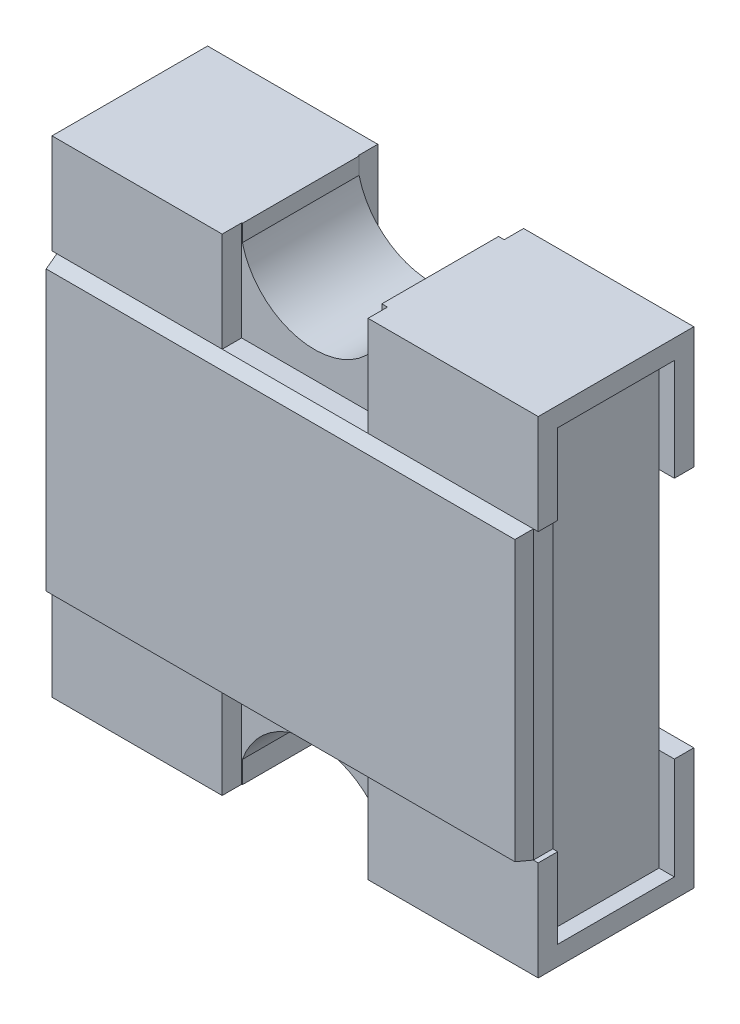
SolidWorks part; units mm, degrees
ref_plane "Спереди" through (0, 0, 0) normal (0, 0, 1) x (1, 0, 0)
ref_plane "Сверху" through (0, 0, 0) normal (0, 1, 0) x (1, 0, 0)
ref_plane "Справа" through (0, 0, 0) normal (1, 0, 0) x (0, 0, -1)
sketch "Эскиз1" plane through (0, 0, 0) normal (0, 0, 1) x (1, 0, 0)
  line L0 (-0.1484, 0.5) -> (-0.1484, 0.4655)
  line L1 (0.1384, 0.5) -> (0.1384, 0.4372)
  line L2 (0, 0) -> (0.4684, 0) construction
  line L3 (0.1384, -0.5) -> (0.1384, -0.4321)
  line L4 (0.4684, 0.5) -> (0.4684, -0.5)
  line L5 (-0.1484, -0.5) -> (-0.1484, -0.4549)
  line L6 (-0.4784, 0.5) -> (-0.4784, -0.5)
  line L9 (0.1384, 0.5) -> (0.4684, 0.5)
  line L11 (0.1384, -0.5) -> (0.4684, -0.5)
  line L13 (-0.1484, 0.5) -> (-0.4784, 0.5)
  line L15 (-0.1484, -0.5) -> (-0.4784, -0.5)
  arc A0 (-0.1484, 0.4655) -> (0.1384, 0.4372) centre (0, 0.5022) ccw
  arc A1 (-0.1484, -0.4549) -> (0.1384, -0.4321) centre (0, -0.5067) cw
  point P7 (-0.0124, -0.35)
  point P9 (-0.015, 0.35)
  point P16 (-0.4784, 0)
  point P17 (0.4684, 0)
  dimension "D1" = 0.33
  dimension "D2" = 0.33
  dimension "D3" = 1
  dimension "D4" = 0.15
  dimension "D5" = 0.15
extrude "Вытянуть1" add sketch "Эскиз1" along normal blind 0.24 from offset 0.04
sketch "Эскиз2" plane through (0, 0, 0) normal (0, 0, 1) x (1, 0, 0)
  line L1 (-0.49, 0.295) -> (0.49, 0.295)
  line L2 (-0.49, 0.295) -> (-0.49, -0.295)
  line L3 (-0.49, -0.295) -> (0.49, -0.295)
  line L4 (0.49, 0.295) -> (0.49, -0.295)
extrude "Бобышка-Вытянуть1" add sketch "Эскиз2" along normal blind 0.03 draft 15 and the other way blind 0.04 from offset 0.32
sketch "Эскиз3" plane through (0, 0, 0) normal (1, 0, 0) x (0, 0, -1)
  line L0 (-0.32, 0.295) -> (-0.28, 0.295)
  line L1 (-0.32, 0.5) -> (0, 0.5)
  line L2 (-0.32, 0.5) -> (-0.32, 0.295)
  line L4 (0, 0.5) -> (0, 0.25)
  line L5 (-0.28, 0.295) -> (-0.28, 0.46)
  line L6 (-0.28, 0.46) -> (-0.04, 0.46)
  line L7 (-0.04, 0.46) -> (-0.04, 0.25)
  line L9 (-0.04, 0.25) -> (0, 0.25)
  line L10 (0, 0) -> (-0.5306, 0) construction
  line L11 (-0.04, -0.25) -> (0, -0.25)
  line L12 (-0.04, -0.46) -> (-0.04, -0.25)
  line L13 (-0.28, -0.46) -> (-0.04, -0.46)
  line L14 (-0.28, -0.295) -> (-0.28, -0.46)
  line L15 (0, -0.5) -> (0, -0.25)
  line L16 (-0.32, -0.5) -> (-0.32, -0.295)
  line L17 (-0.32, -0.5) -> (0, -0.5)
  line L18 (-0.32, -0.295) -> (-0.28, -0.295)
extrude "Бобышка-Вытянуть4" add sketch "Эскиз3<2>" along normal blind 0.35 from offset 0.5 offset against normal yes
sketch "Эскиз3<2>" plane through (0, 0, 0) normal (1, 0, 0) x (0, 0, -1) same geometry as "Эскиз3"
extrude "Бобышка-Вытянуть5" add sketch "Эскиз3" against normal blind 0.35 from offset 0.5
